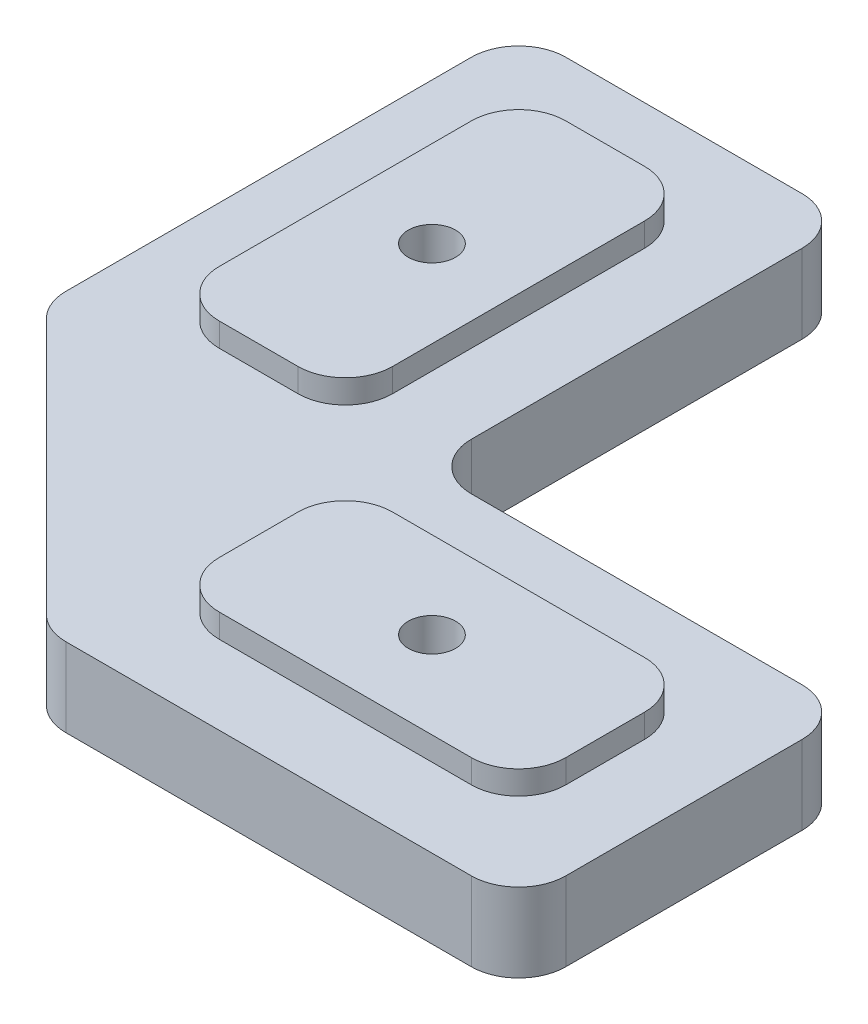
SolidWorks part; units mm, degrees
ref_plane "Alzado" through (0, 0, 0) normal (0, 0, 1) x (1, 0, 0)
ref_plane "Planta" through (0, 0, 0) normal (0, 1, 0) x (1, 0, 0)
ref_plane "Vista lateral" through (0, 0, 0) normal (1, 0, 0) x (0, 0, -1)
sketch "Croquis1" plane through (0, 0, 0) normal (0, 1, 0) x (1, 0, 0)
  line L1 (3, 38) -> (8, 38)
  line L2 (0, 35) -> (0, 19)
  line L3 (3, 16) -> (8, 16)
  line L4 (11, 35) -> (11, 19)
  line L5 (19, 11) -> (35, 11)
  line L6 (16, 8) -> (16, 3)
  line L7 (19, 0) -> (35, 0)
  line L8 (38, 8) -> (38, 3)
  arc A0 (35, 0) -> (38, 3) centre (35, 3) ccw
  arc A1 (35, 11) -> (38, 8) centre (35, 8) cw
  arc A2 (19, 11) -> (16, 8) centre (19, 8) ccw
  arc A3 (16, 3) -> (19, 0) centre (19, 3) ccw
  arc A4 (0, 19) -> (3, 16) centre (3, 19) ccw
  arc A5 (8, 16) -> (11, 19) centre (8, 19) ccw
  arc A6 (8, 38) -> (11, 35) centre (8, 35) cw
  arc A7 (3, 38) -> (0, 35) centre (3, 35) ccw
  point P17 (16, 0)
  point P20 (0, 16)
  point P23 (11, 16)
  point P26 (11, 38)
  point P29 (0, 38)
  dimension "D5" = 3
  dimension "D1" = 11
  dimension "D2" = 22
  dimension "D3" = 38
  dimension "D4" = 38
extrude "Saliente-Extruir1" add sketch "Croquis1" along normal blind 1.5
sketch "Croquis2" plane through (0, 0, 0) normal (0, 1, 0) x (1, 0, 0)
  line L0 (-2, 43) -> (13, 43)
  line L1 (16, 40) -> (16, 19)
  line L2 (19, 16) -> (40, 16)
  line L3 (43, 13) -> (43, -2)
  line L4 (40, -5) -> (14.2691, -5)
  line L5 (12.1478, -4.1213) -> (-4.1213, 12.1478)
  line L6 (-5, 14.2691) -> (-5, 40)
  line L7 (11, 19) -> (11, 35) construction
  line L8 (8, 38) -> (3, 38) construction
  line L9 (0, 35) -> (0, 19) construction
  line L10 (35, 11) -> (19, 11) construction
  line L11 (38, 3) -> (38, 8) construction
  line L12 (19, 0) -> (35, 0) construction
  arc A0 (-4.1213, 12.1478) -> (-5, 14.2691) centre (-2, 14.2691) cw
  arc A1 (14.2691, -5) -> (12.1478, -4.1213) centre (14.2691, -2) cw
  arc A2 (43, -2) -> (40, -5) centre (40, -2) cw
  arc A3 (40, 16) -> (43, 13) centre (40, 13) cw
  arc A4 (16, 19) -> (19, 16) centre (19, 19) ccw
  arc A5 (13, 43) -> (16, 40) centre (13, 40) cw
  arc A6 (-2, 43) -> (-5, 40) centre (-2, 40) ccw
  point P31 (16, 43)
  dimension "D7" = 3
  dimension "D1" = 5
  dimension "D2" = 5
  dimension "D3" = 5
  dimension "D4" = 5
  dimension "D5" = 5
  dimension "D6" = 5
extrude "Saliente-Extruir2" add sketch "Croquis2" against normal blind 5
sketch "Croquis3" plane through (0, 1.5, 0) normal (0, 1, 0) x (1, 0, 0)
  line L1 (8, 38) -> (3, 38) construction
  line L2 (11, 19) -> (11, 35) construction
  circle A0 centre (5.5, 27) radius 1.5
  point P4 (5.5, 38)
  dimension "D3" = 3
  dimension "D1" = 11
  dimension "D2" = 5.5
extrude "Cortar-Extruir1" cut sketch "Croquis3" against normal blind 45
sketch "Croquis4" plane through (0, -5, 0) normal (0, -1, 0) x (1, 0, 0)
  line L1 (2.6693, -28.7891) -> (5.634, -30.3459)
  line L2 (5.634, -30.3459) -> (8.4647, -28.5569)
  line L3 (8.4647, -28.5569) -> (8.3307, -25.2109)
  line L4 (8.3307, -25.2109) -> (5.366, -23.6541)
  line L5 (5.366, -23.6541) -> (2.5353, -25.4431)
  line L6 (2.5353, -25.4431) -> (2.6693, -28.7891)
  circle A0 centre (5.5, -27) radius 2.9 construction
  dimension "D1" = 5.8
extrude "Cortar-Extruir2" cut sketch "Croquis4" against normal blind 2.3
sketch "Croquis5" plane through (0, 1.5, 0) normal (0, 1, 0) x (1, 0, 0)
  line L0 (38, 3) -> (38, 8) construction
  line L1 (19, 0) -> (35, 0) construction
  circle A0 centre (27, 5.5) radius 1.5
  dimension "D3" = 3
  dimension "D1" = 11
  dimension "D2" = 5.5
extrude "Cortar-Extruir3" cut sketch "Croquis5" against normal blind 42.3
sketch "Croquis8" plane through (0, -5, 0) normal (0, -1, 0) x (1, 0, 0)
  line L1 (24.2506, -3.5884) -> (23.9698, -6.9253)
  line L2 (23.9698, -6.9253) -> (26.7193, -8.8368)
  line L3 (26.7193, -8.8368) -> (29.7494, -7.4116)
  line L4 (29.7494, -7.4116) -> (30.0302, -4.0747)
  line L5 (30.0302, -4.0747) -> (27.2807, -2.1632)
  line L6 (27.2807, -2.1632) -> (24.2506, -3.5884)
  circle A0 centre (27, -5.5) radius 2.9 construction
  dimension "D1" = 5.8
extrude "Cortar-Extruir4" cut sketch "Croquis8" against normal blind 2.3
ref_axis "Eje1" through (5.5, -33.4232, -27) along (0, 1, 0)
ref_axis "Eje2" through (27, -27.5904, -5.5) along (0, 1, 0)
